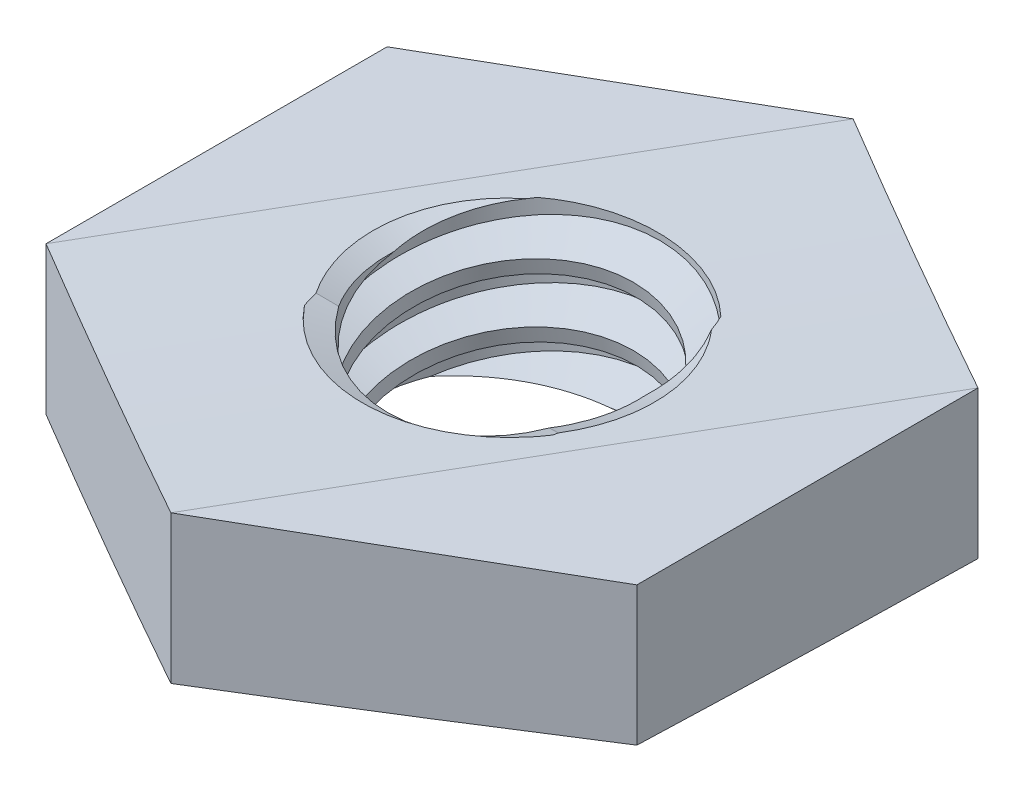
SolidWorks part; units mm, degrees
ref_plane "Front" through (0, 0, 0) normal (0, 0, 1) x (1, 0, 0)
ref_plane "Top" through (0, 0, 0) normal (0, 1, 0) x (1, 0, 0)
ref_plane "Right" through (0, 0, 0) normal (1, 0, 0) x (0, 0, -1)
sketch "Sketch1" plane through (0, 0, 0) normal (0, 1, 0) x (1, 0, 0)
  line L1 (0, 2.3094) -> (-2, 1.1547)
  line L2 (-2, 1.1547) -> (-2, -1.1547)
  line L3 (-2, -1.1547) -> (0, -2.3094)
  line L4 (0, -2.3094) -> (2, -1.1547)
  line L5 (2, -1.1547) -> (2, 1.1547)
  line L6 (2, 1.1547) -> (0, 2.3094)
  circle A0 centre (0, 0) radius 2 construction
  dimension "Hex Flats" = 4
extrude "Extrude1" add sketch "Sketch1" along normal mid plane 1.6
sketch "Sketch2" plane through (0, 0, 0) normal (1, 0, 0) x (0, 0, -1)
  line L0 (-1, -0.8) -> (-1, 0.8) construction
  line L1 (0, -0.8) -> (1, -0.8)
  line L2 (0, -0.8) -> (0, 0.8)
  line L3 (0, 0.8) -> (1, 0.8)
  line L4 (1, -0.8) -> (1, 0.8)
  line L5 (-1.1547, 0.8) -> (1.1547, 0.8) construction
  line L6 (-1.1547, -0.8) -> (1.1547, -0.8) construction
  line L7 (0, -1.8) -> (0, -0.8) construction
  dimension "Thread Dia" = 2
revolve "Revolve1" add sketch "Sketch2" angle 360 about L7
sketch "Sketch3" plane through (0, 0, 0) normal (1, 0, 0) x (0, 0, -1)
  line L0 (1, 0.8) -> (-1, 0.8) construction
  line L1 (-1, 0.8) -> (-1, 0.4) construction
  line L2 (-1, 0.4) -> (1, 0.8) construction
  line L3 (1, 0.8) -> (1.0098, 0.751) construction
  line L4 (1.0098, 0.751) -> (1.0784, 0.4078)
  line L5 (1.0784, 0.4078) -> (0.8416, 0.4879)
  line L6 (0.8416, 0.4879) -> (0.822, 0.5859)
  line L7 (0.822, 0.5859) -> (1.0098, 0.751)
  line L8 (0.8318, 0.5369) -> (1.0441, 0.5794) construction
  line L9 (1, 0.8) -> (1, 0.5705) construction
  line L10 (1, 0.5705) -> (-1, 0.1705) construction
  line L11 (-1, 0.1705) -> (-1, 0.4) construction
  line L12 (-0.0859, 0.8) -> (0.0859, -0.0589) construction
  line L13 (-1, -0.8) -> (-1, 0.8) construction
  line L14 (0, 0.8) -> (1, 0.8) construction
  line L15 (1, -0.8) -> (1, 0.8) construction
  line L16 (0, 0) -> (0, 0.8) construction
  line L17 (-1.0098, 0.751) -> (-1.0784, 0.4078) construction
  line L18 (-0.822, 0.5859) -> (-1.0098, 0.751) construction
  line L19 (-0.8416, 0.4879) -> (-0.822, 0.5859) construction
  line L20 (-1.0784, 0.4078) -> (-0.8416, 0.4879) construction
  line L21 (0.0859, 0.8) -> (-0.0859, -0.0589) construction
  point P13 (0, 0.3705)
  dimension "D1" = 0.05
  dimension "D2" = 0.1
  dimension "Thread Pitch" = 0.4
  dimension "D4" = 60
  dimension "D5" = 0.4
revolve "Cut-Revolve1" cut sketch "Sketch3" angle 360 about L12
pattern_linear "LPattern1" count 4 spacing 0.4 along (0, -1, 0) count 2 spacing 0.4 along (0, 1, 0) of "Cut-Revolve1"
sketch "Sketch4" plane through (0, 0, 0) normal (1, 0, 0) x (0, 0, -1)
  line L0 (0, 0.8) -> (1, 0.8)
  line L1 (1, 0.8) -> (0.822, 0.717)
  line L2 (0.822, 0.717) -> (0.822, -0.717)
  line L3 (0.822, -0.717) -> (1, -0.8)
  line L4 (1, -0.8) -> (0, -0.8)
  line L5 (0, -0.8) -> (0, 0.8)
  line L6 (1, -0.8) -> (1, 0.8) construction
  line L7 (0, 0.8) -> (1, 0.8) construction
  line L8 (0, -0.8) -> (1, -0.8) construction
  line L9 (0, -0.8) -> (0, 0.8) construction
  line L10 (0, 0.8) -> (0, 0.9964) construction
  dimension "D1" = 25
revolve "Cut-Revolve2" cut sketch "Sketch4" angle 360 about L10
combine bodies "Combine1" operation type subtract main body 112 bodies to subtract 111
sketch "Sketch5" plane through (0, 0, 0) normal (1, 0, 0) x (0, 0, -1)
  line L0 (0, -0.8) -> (2, -0.8)
  line L1 (2, -0.8) -> (2.3094, -0.6557)
  line L2 (2.3094, -0.6557) -> (2.3094, 0.6557)
  line L3 (2.3094, 0.6557) -> (2, 0.8)
  line L4 (0, 0.8) -> (0, 2.07)
  line L5 (0, 2.07) -> (3.5794, 2.07)
  line L6 (3.5794, 2.07) -> (3.5794, -2.07)
  line L7 (3.5794, -2.07) -> (0, -2.07)
  line L8 (0, -2.07) -> (0, -0.8)
  line L9 (2, 0.8) -> (2, -0.8) construction
  line L11 (0, -0.8) -> (1, -0.8) construction
  line L12 (2, 0.8) -> (0, 0.8)
  line L13 (2.3094, 0) -> (3.5794, 0) construction
  line L14 (2.3094, 0.8) -> (2.3094, -0.8) construction
  line L15 (0, -0.8) -> (0, 0.8) construction
  line L17 (0, 0) -> (2, 0) construction
  line L22 (0, 0.8) -> (1, 0.8) construction
  dimension "D1" = 25
  dimension "D2" = 1.27
  dimension "D3" = 1.6
sketch "Sketch6" plane through (-1, 0, -1.7321) normal (-0.5, 0, -0.866) x (-0.866, 0, 0.5)
  point P0 (0, 0)
sketch "Sketch7" plane through (0, 0.8, 0) normal (0, 1, 0) x (1, 0, 0)
  point P0 (-0.7985, 1.3813)
sketch "Sketch8" plane through (1, 0, -1.7321) normal (0.5, 0, -0.866) x (-0.866, 0, -0.5)
  arc A0 (-9.371, 2.182) -> (9.371, 2.182) centre (0, 32.7792) ccw construction
  arc A1 (-10.6452, 1.5433) -> (10.6452, 1.5433) centre (0, 32.7792) ccw construction
  arc A2 (-9.371, 2.182) -> (9.371, 2.182) centre (0, 32.7792) ccw
  arc A3 (-10.6452, 1.5433) -> (10.6452, 1.5433) centre (0, 32.7792) ccw
  spline S0 degree 2 poles (10.6452, 1.5433) (-0.0818, -7.5014) (-10.6452, 1.5433) knots 0 0 0 1 1 1
  spline S1 degree 2 poles (9.371, 2.182) (-0.3791, 7.6693) (-9.371, 2.182) knots 0 0 0 1 1 1
extrude "Cut-Extrude1" cut sketch "Sketch8" against normal blind 10
equation "\"D1@Sketch3\"=\"Thread Pitch@Sketch3\"/8"
equation "\"D2@Sketch3\"=\"Thread Pitch@Sketch3\"/4"
equation "\"D5@Sketch3\"=\"Thread Pitch@Sketch3\""
equation "\"D4@LPattern1\"=\"Thread Pitch@Sketch3\""
equation "\"D3@LPattern1\"=\"Thread Pitch@Sketch3\""
equation "\"D1@LPattern1\"=\"Height@Extrude1\"/\"Thread Pitch@Sketch3\""
